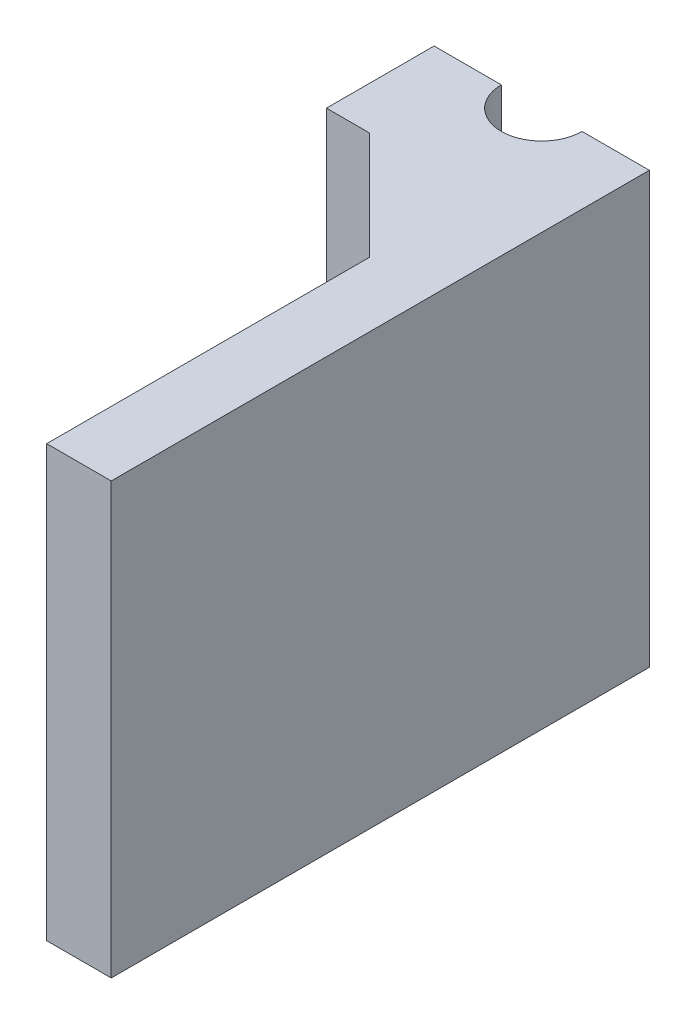
SolidWorks part; units mm, degrees
ref_plane "Front Plane" through (0, 0, 0) normal (1, 0, 0) x (0, 1, 0)
ref_plane "Top Plane" through (0, 0, 0) normal (0, 0, 1) x (0, 1, 0)
ref_plane "Right Plane" through (0, 0, 0) normal (0, 1, 0) x (-1, 0, 0)
sketch "Sketch2" plane through (0, 0, 0) normal (1, 0, 0) x (0, 1, 0)
  line L0 (0, -7.5) -> (-4, -7.5)
  line L1 (-10, -7.5) -> (10, -7.5)
  line L2 (-10, -7.5) -> (-10, 7.5)
  line L3 (-10, 7.5) -> (10, 7.5)
  line L4 (10, -7.5) -> (10, 7.5)
  line L5 (-10, -7.5) -> (10, 7.5) construction
  line L6 (-10, 7.5) -> (10, -7.5) construction
  line L11 (-5, -9.5) -> (5, -5.5) construction
  line L12 (-5, -5.5) -> (5, -9.5) construction
  line L13 (-4, -7.5) -> (-5, -5.5)
  line L14 (0, -7.5) -> (4, -7.5)
  line L15 (4, -7.5) -> (5, -5.5)
  line L16 (-5, -5.5) -> (5, -5.5)
  line L22 (-2.5, -3) -> (2.5, -3)
  line L23 (-2.5, -3) -> (-2.5, -5.5)
  line L24 (-2.5, -5.5) -> (2.5, -5.5)
  line L25 (2.5, -3) -> (2.5, -5.5)
  point P0 (0, 0)
  point P6 (0, -7.5)
  dimension "D1" = 20
  dimension "D2" = 15
  dimension "D3" = 10
  dimension "D4" = 4
  dimension "D6" = 2.5
  dimension "D7" = 5
extrude "Boss-Extrude1" add sketch "Sketch2" along normal blind 10 contours L22 L25 L16 L15 L1 L4 L3 L2 L13 L23 region at (0, 0, 0.6288)
sketch "Sketch4" plane through (0, 0, -3) normal (0, 0, -1) x (1, 0, 0)
  line L0 (5, 2.5) -> (2, 2.5)
  line L1 (10, 2.5) -> (0, 2.5) construction
  line L2 (2, 2.5) -> (2, -2.5)
  line L3 (10, -2.5) -> (0, -2.5) construction
  line L4 (2, -2.5) -> (8, -2.5)
  line L5 (8, -2.5) -> (8, 2.5)
  line L6 (8, 2.5) -> (5, 2.5)
extrude "Cut-Extrude2" cut sketch "Sketch4" against normal blind 4.88
sketch "Sketch6" plane through (0, 2.5, 0) normal (0, -1, 0) x (1, 0, 0)
  line L1 (2, 1.88) -> (8, 1.88)
  line L2 (2, 1.88) -> (2, -4.12)
  line L3 (2, -4.12) -> (8, -4.12)
  line L4 (8, 1.88) -> (8, -4.12)
  circle A0 centre (5, -1.12) radius 1.875
  dimension "D1" = 6
extrude "Cut-Extrude3" [suppressed] cut sketch "Sketch6" along normal through all both and the other way through all draft 1 contours A0
extrude "Cut-Extrude4" cut sketch "Sketch6<3>" against normal through all both and the other way through all contours A0 region at (5, 2.5, -1.12)
sketch "Sketch6<3>" plane through (0, 2.5, 0) normal (0, -1, 0) x (1, 0, 0) same geometry as "Sketch6"
sketch "Sketch7" plane through (0, 10, 0) normal (0, 1, 0) x (-1, 0, 0)
  line L0 (-5, -1.12) -> (-10, -1.12)
  line L1 (-10, -7.5) -> (-10, 7.5) construction
  line L2 (0, -7.5) -> (0, 7.5) construction
  line L3 (-10, -1.12) -> (0, -1.12)
  line L4 (-10, -1.12) -> (-10, 3.88)
  line L5 (-10, 3.88) -> (0, 3.88)
  line L6 (0, -1.12) -> (0, 3.88)
  circle M2 centre (-5, -1.12) radius 1.875
  line M3 (0, -7.5) -> (0, 7.5)
  line M5 (-10, 7.5) -> (-10, -7.5)
  dimension "D1" = 5
extrude "Cut-Extrude5" cut sketch "Sketch7" against normal through all both and the other way through all flip side to cut contours L5 L0 L3 M5 M2 M3 region at (5, 10, 1.5916)
sketch "Sketch8" plane through (0, 0, 3.88) normal (0, 0, 1) x (1, 0, 0)
  line L0 (10, -10) -> (0, -10) construction
  line L1 (10, 10) -> (7, 10)
  line L2 (10, 10) -> (10, -10)
  line L3 (10, -10) -> (7, -10)
  line L4 (7, 10) -> (7, -10)
  dimension "D1" = 3
extrude "Boss-Extrude2" add sketch "Sketch8" along normal blind 20
chamfer "Chamfer1" distance 5 angle 45 1 edges at (7, 0, 3.88)
